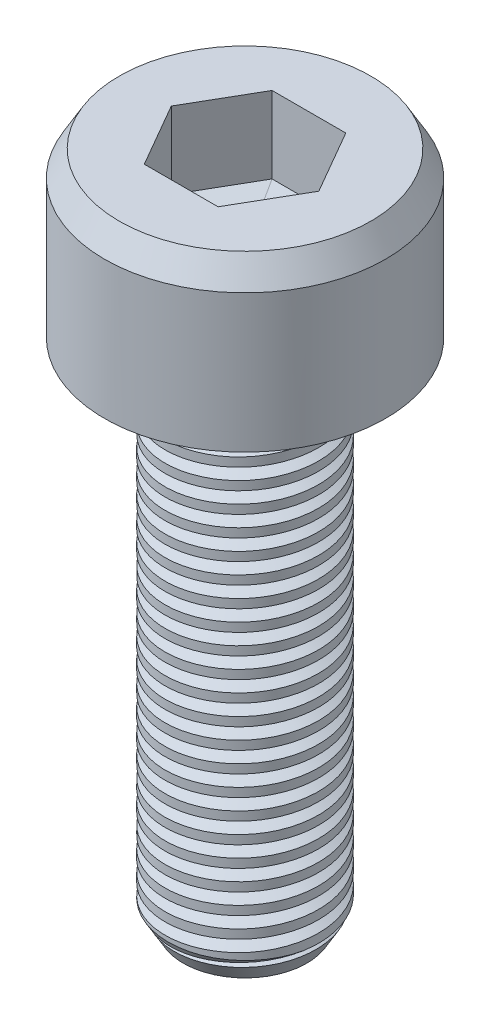
SolidWorks part; units mm, degrees
ref_plane "Front Plane" through (0, 0, 0) normal (0, 0, 1) x (1, 0, 0)
ref_plane "Top Plane" through (0, 0, 0) normal (0, 1, 0) x (1, 0, 0)
ref_plane "Right Plane" through (0, 0, 0) normal (1, 0, 0) x (0, 0, -1)
sketch "Sketch1" plane through (0, 0, 0) normal (0, 1, 0) x (1, 0, 0)
  circle A0 centre (0, 0) radius 2.75
  dimension "D1" = 5.5
extrude "Boss-Extrude1" add sketch "Sketch1" along normal blind 2.7
sketch "Sketch2" plane through (0, 2.7, 0) normal (0, 1, 0) x (1, 0, 0)
  circle A0 centre (0, 0) radius 2.75
  circle A1 centre (0, 0) radius 2.75 construction
  dimension "D1" = 5.5
extrude "Boss-Extrude2" add sketch "Sketch2" along normal blind 0.5 draft 30
sketch "Sketch5" plane through (0, 3.2, 0) normal (0, 1, 0) x (1, 0, 0)
  line L1 (1.4434, 0) -> (0.7217, 1.25)
  line L2 (0.7217, 1.25) -> (-0.7217, 1.25)
  line L3 (-0.7217, 1.25) -> (-1.4434, 0)
  line L4 (-1.4434, 0) -> (-0.7217, -1.25)
  line L5 (-0.7217, -1.25) -> (0.7217, -1.25)
  line L6 (0.7217, -1.25) -> (1.4434, 0)
  circle A0 centre (0, 0) radius 1.25 construction
  circle A1 centre (0, 0) radius 2.4613 construction
  dimension "D1" = 2.5
extrude "Cut-Extrude3" cut sketch "Sketch5" against normal blind 1.5
sketch "Sketch6" plane through (0, 1.7, 0) normal (0, 1, 0) x (1, 0, 0)
  line L0 (1.4434, 0) -> (0.7217, 1.25) construction
  line L1 (1.4434, 0) -> (0.7217, 1.25)
  line L2 (0.7217, 1.25) -> (-0.7217, 1.25)
  line L3 (-0.7217, 1.25) -> (-1.4434, 0)
  line L4 (-1.4434, 0) -> (-0.7217, -1.25)
  line L5 (-0.7217, -1.25) -> (0.7217, -1.25)
  line L6 (0.7217, -1.25) -> (1.4434, 0)
  circle A0 centre (0, 0) radius 1.25 construction
extrude "Cut-Extrude4" cut sketch "Sketch6" against normal blind 0.25 draft 80
sketch "Sketch7" plane through (0, 0, 0) normal (0, -1, 0) x (1, 0, 0)
  circle A0 centre (0, 0) radius 1.5
  circle A1 centre (0, 0) radius 2.75 construction
  dimension "D1" = 3
extrude "Boss-Extrude3" add sketch "Sketch7" along normal blind 9.5
sketch "Sketch8" plane through (0, -9.5, 0) normal (0, -1, 0) x (1, 0, 0)
  circle A0 centre (0, 0) radius 1.5
  circle A1 centre (0, 0) radius 1.5 construction
  dimension "D1" = 3
extrude "Boss-Extrude4" add sketch "Sketch8" along normal blind 0.5 draft 30
sketch "Sketch9" plane through (0, -10, 0) normal (0, -1, 0) x (1, 0, 0)
  circle A0 centre (0, 0) radius 1.5
  circle A1 centre (0, 0) radius 1.2113 construction
  dimension "D1" = 3
curve "Helix/Spiral1" pitch 0.4 height 10 radius 1.5 centre (0, -10, 0) axis (0, 1, 0) start towards (1, 0, 0)
sketch "Sketch10" plane through (0, 0, 0) normal (0, 0, 1) x (1, 0, 0)
  line L1 (1.3037, -10) -> (1.5981, -10.17)
  line L2 (1.5981, -10.17) -> (1.5981, -9.83)
  line L3 (1.5981, -9.83) -> (1.3037, -10)
  circle A0 centre (1.5, -10) radius 0.0981 construction
  spline S0 degree 3 poles (1.5, -10) (1.5, -9.9917) (1.4219, -9.975) (1.0883, -9.95) (0.589, -9.925) (0, -9.9) (-0.589, -9.875) (-1.0883, -9.85) (-1.4219, -9.825) (-1.5391, -9.8) (-1.4219, -9.775) (-1.0883, -9.75) (-0.589, -9.725) (0, -9.7) (0.589, -9.675) (1.0883, -9.65) (1.4219, -9.625) (1.5391, -9.6) (1.4219, -9.575) (1.0883, -9.55) (0.589, -9.525) (0, -9.5) (-0.589, -9.475) (-1.0883, -9.45) (-1.4219, -9.425) (-1.5391, -9.4) (-1.4219, -9.375) (-1.0883, -9.35) (-0.589, -9.325) (0, -9.3) (0.589, -9.275) (1.0883, -9.25) (1.4219, -9.225) (1.5391, -9.2) (1.4219, -9.175) (1.0883, -9.15) (0.589, -9.125) (0, -9.1) (-0.589, -9.075) (-1.0883, -9.05) (-1.4219, -9.025) (-1.5391, -9) (-1.4219, -8.975) (-1.0883, -8.95) (-0.589, -8.925) (0, -8.9) (0.589, -8.875) (1.0883, -8.85) (1.4219, -8.825) (1.5391, -8.8) (1.4219, -8.775) (1.0883, -8.75) (0.589, -8.725) (0, -8.7) (-0.589, -8.675) (-1.0883, -8.65) (-1.4219, -8.625) (-1.5391, -8.6) (-1.4219, -8.575) (-1.0883, -8.55) (-0.589, -8.525) (0, -8.5) (0.589, -8.475) (1.0883, -8.45) (1.4219, -8.425) (1.5391, -8.4) (1.4219, -8.375) (1.0883, -8.35) (0.589, -8.325) (0, -8.3) (-0.589, -8.275) (-1.0883, -8.25) (-1.4219, -8.225) (-1.5391, -8.2) (-1.4219, -8.175) (-1.0883, -8.15) (-0.589, -8.125) (0, -8.1) (0.589, -8.075) (1.0883, -8.05) (1.4219, -8.025) (1.5391, -8) (1.4219, -7.975) (1.0883, -7.95) (0.589, -7.925) (0, -7.9) (-0.589, -7.875) (-1.0883, -7.85) (-1.4219, -7.825) (-1.5391, -7.8) (-1.4219, -7.775) (-1.0883, -7.75) (-0.589, -7.725) (0, -7.7) (0.589, -7.675) (1.0883, -7.65) (1.4219, -7.625) (1.5391, -7.6) (1.4219, -7.575) (1.0883, -7.55) (0.589, -7.525) (0, -7.5) (-0.589, -7.475) (-1.0883, -7.45) (-1.4219, -7.425) (-1.5391, -7.4) (-1.4219, -7.375) (-1.0883, -7.35) (-0.589, -7.325) (0, -7.3) (0.589, -7.275) (1.0883, -7.25) (1.4219, -7.225) (1.5391, -7.2) (1.4219, -7.175) (1.0883, -7.15) (0.589, -7.125) (0, -7.1) (-0.589, -7.075) (-1.0883, -7.05) (-1.4219, -7.025) (-1.5391, -7) (-1.4219, -6.975) (-1.0883, -6.95) (-0.589, -6.925) (0, -6.9) (0.589, -6.875) (1.0883, -6.85) (1.4219, -6.825) (1.5391, -6.8) (1.4219, -6.775) (1.0883, -6.75) (0.589, -6.725) (0, -6.7) (-0.589, -6.675) (-1.0883, -6.65) (-1.4219, -6.625) (-1.5391, -6.6) (-1.4219, -6.575) (-1.0883, -6.55) (-0.589, -6.525) (0, -6.5) (0.589, -6.475) (1.0883, -6.45) (1.4219, -6.425) (1.5391, -6.4) (1.4219, -6.375) (1.0883, -6.35) (0.589, -6.325) (0, -6.3) (-0.589, -6.275) (-1.0883, -6.25) (-1.4219, -6.225) (-1.5391, -6.2) (-1.4219, -6.175) (-1.0883, -6.15) (-0.589, -6.125) (0, -6.1) (0.589, -6.075) (1.0883, -6.05) (1.4219, -6.025) (1.5391, -6) (1.4219, -5.975) (1.0883, -5.95) (0.589, -5.925) (0, -5.9) (-0.589, -5.875) (-1.0883, -5.85) (-1.4219, -5.825) (-1.5391, -5.8) (-1.4219, -5.775) (-1.0883, -5.75) (-0.589, -5.725) (0, -5.7) (0.589, -5.675) (1.0883, -5.65) (1.4219, -5.625) (1.5391, -5.6) (1.4219, -5.575) (1.0883, -5.55) (0.589, -5.525) (0, -5.5) (-0.589, -5.475) (-1.0883, -5.45) (-1.4219, -5.425) (-1.5391, -5.4) (-1.4219, -5.375) (-1.0883, -5.35) (-0.589, -5.325) (0, -5.3) (0.589, -5.275) (1.0883, -5.25) (1.4219, -5.225) (1.5391, -5.2) (1.4219, -5.175) (1.0883, -5.15) (0.589, -5.125) (0, -5.1) (-0.589, -5.075) (-1.0883, -5.05) (-1.4219, -5.025) (-1.5391, -5) (-1.4219, -4.975) (-1.0883, -4.95) (-0.589, -4.925) (0, -4.9) (0.589, -4.875) (1.0883, -4.85) (1.4219, -4.825) (1.5391, -4.8) (1.4219, -4.775) (1.0883, -4.75) (0.589, -4.725) (0, -4.7) (-0.589, -4.675) (-1.0883, -4.65) (-1.4219, -4.625) (-1.5391, -4.6) (-1.4219, -4.575) (-1.0883, -4.55) (-0.589, -4.525) (0, -4.5) (0.589, -4.475) (1.0883, -4.45) (1.4219, -4.425) (1.5391, -4.4) (1.4219, -4.375) (1.0883, -4.35) (0.589, -4.325) (0, -4.3) (-0.589, -4.275) (-1.0883, -4.25) (-1.4219, -4.225) (-1.5391, -4.2) (-1.4219, -4.175) (-1.0883, -4.15) (-0.589, -4.125) (0, -4.1) (0.589, -4.075) (1.0883, -4.05) (1.4219, -4.025) (1.5391, -4) (1.4219, -3.975) (1.0883, -3.95) (0.589, -3.925) (0, -3.9) (-0.589, -3.875) (-1.0883, -3.85) (-1.4219, -3.825) (-1.5391, -3.8) (-1.4219, -3.775) (-1.0883, -3.75) (-0.589, -3.725) (0, -3.7) (0.589, -3.675) (1.0883, -3.65) (1.4219, -3.625) (1.5391, -3.6) (1.4219, -3.575) (1.0883, -3.55) (0.589, -3.525) (0, -3.5) (-0.589, -3.475) (-1.0883, -3.45) (-1.4219, -3.425) (-1.5391, -3.4) (-1.4219, -3.375) (-1.0883, -3.35) (-0.589, -3.325) (0, -3.3) (0.589, -3.275) (1.0883, -3.25) (1.4219, -3.225) (1.5391, -3.2) (1.4219, -3.175) (1.0883, -3.15) (0.589, -3.125) (0, -3.1) (-0.589, -3.075) (-1.0883, -3.05) (-1.4219, -3.025) (-1.5391, -3) (-1.4219, -2.975) (-1.0883, -2.95) (-0.589, -2.925) (0, -2.9) (0.589, -2.875) (1.0883, -2.85) (1.4219, -2.825) (1.5391, -2.8) (1.4219, -2.775) (1.0883, -2.75) (0.589, -2.725) (0, -2.7) (-0.589, -2.675) (-1.0883, -2.65) (-1.4219, -2.625) (-1.5391, -2.6) (-1.4219, -2.575) (-1.0883, -2.55) (-0.589, -2.525) (0, -2.5) (0.589, -2.475) (1.0883, -2.45) (1.4219, -2.425) (1.5391, -2.4) (1.4219, -2.375) (1.0883, -2.35) (0.589, -2.325) (0, -2.3) (-0.589, -2.275) (-1.0883, -2.25) (-1.4219, -2.225) (-1.5391, -2.2) (-1.4219, -2.175) (-1.0883, -2.15) (-0.589, -2.125) (0, -2.1) (0.589, -2.075) (1.0883, -2.05) (1.4219, -2.025) (1.5391, -2) (1.4219, -1.975) (1.0883, -1.95) (0.589, -1.925) (0, -1.9) (-0.589, -1.875) (-1.0883, -1.85) (-1.4219, -1.825) (-1.5391, -1.8) (-1.4219, -1.775) (-1.0883, -1.75) (-0.589, -1.725) (0, -1.7) (0.589, -1.675) (1.0883, -1.65) (1.4219, -1.625) (1.5391, -1.6) (1.4219, -1.575) (1.0883, -1.55) (0.589, -1.525) (0, -1.5) (-0.589, -1.475) (-1.0883, -1.45) (-1.4219, -1.425) (-1.5391, -1.4) (-1.4219, -1.375) (-1.0883, -1.35) (-0.589, -1.325) (0, -1.3) (0.589, -1.275) (1.0883, -1.25) (1.4219, -1.225) (1.5391, -1.2) (1.4219, -1.175) (1.0883, -1.15) (0.589, -1.125) (0, -1.1) (-0.589, -1.075) (-1.0883, -1.05) (-1.4219, -1.025) (-1.5391, -1) (-1.4219, -0.975) (-1.0883, -0.95) (-0.589, -0.925) (0, -0.9) (0.589, -0.875) (1.0883, -0.85) (1.4219, -0.825) (1.5391, -0.8) (1.4219, -0.775) (1.0883, -0.75) (0.589, -0.725) (0, -0.7) (-0.589, -0.675) (-1.0883, -0.65) (-1.4219, -0.625) (-1.5391, -0.6) (-1.4219, -0.575) (-1.0883, -0.55) (-0.589, -0.525) (0, -0.5) (0.589, -0.475) (1.0883, -0.45) (1.4219, -0.425) (1.5391, -0.4) (1.4219, -0.375) (1.0883, -0.35) (0.589, -0.325) (0, -0.3) (-0.589, -0.275) (-1.0883, -0.25) (-1.4219, -0.225) (-1.5391, -0.2) (-1.4219, -0.175) (-1.0883, -0.15) (-0.589, -0.125) (0, -0.1) (0.589, -0.075) (1.0883, -0.05) (1.4219, -0.025) (1.5, -0.0083) (1.5, 0) knots 0 0 0 0 0.0025 0.005 0.0075 0.01 0.0125 0.015 0.0175 0.02 0.0225 0.025 0.0275 0.03 0.0325 0.035 0.0375 0.04 0.0425 0.045 0.0475 0.05 0.0525 0.055 0.0575 0.06 0.0625 0.065 0.0675 0.07 0.0725 0.075 0.0775 0.08 0.0825 0.085 0.0875 0.09 0.0925 0.095 0.0975 0.1 0.1025 0.105 0.1075 0.11 0.1125 0.115 0.1175 0.12 0.1225 0.125 0.1275 0.13 0.1325 0.135 0.1375 0.14 0.1425 0.145 0.1475 0.15 0.1525 0.155 0.1575 0.16 0.1625 0.165 0.1675 0.17 0.1725 0.175 0.1775 0.18 0.1825 0.185 0.1875 0.19 0.1925 0.195 0.1975 0.2 0.2025 0.205 0.2075 0.21 0.2125 0.215 0.2175 0.22 0.2225 0.225 0.2275 0.23 0.2325 0.235 0.2375 0.24 0.2425 0.245 0.2475 0.25 0.2525 0.255 0.2575 0.26 0.2625 0.265 0.2675 0.27 0.2725 0.275 0.2775 0.28 0.2825 0.285 0.2875 0.29 0.2925 0.295 0.2975 0.3 0.3025 0.305 0.3075 0.31 0.3125 0.315 0.3175 0.32 0.3225 0.325 0.3275 0.33 0.3325 0.335 0.3375 0.34 0.3425 0.345 0.3475 0.35 0.3525 0.355 0.3575 0.36 0.3625 0.365 0.3675 0.37 0.3725 0.375 0.3775 0.38 0.3825 0.385 0.3875 0.39 0.3925 0.395 0.3975 0.4 0.4025 0.405 0.4075 0.41 0.4125 0.415 0.4175 0.42 0.4225 0.425 0.4275 0.43 0.4325 0.435 0.4375 0.44 0.4425 0.445 0.4475 0.45 0.4525 0.455 0.4575 0.46 0.4625 0.465 0.4675 0.47 0.4725 0.475 0.4775 0.48 0.4825 0.485 0.4875 0.49 0.4925 0.495 0.4975 0.5 0.5025 0.505 0.5075 0.51 0.5125 0.515 0.5175 0.52 0.5225 0.525 0.5275 0.53 0.5325 0.535 0.5375 0.54 0.5425 0.545 0.5475 0.55 0.5525 0.555 0.5575 0.56 0.5625 0.565 0.5675 0.57 0.5725 0.575 0.5775 0.58 0.5825 0.585 0.5875 0.59 0.5925 0.595 0.5975 0.6 0.6025 0.605 0.6075 0.61 0.6125 0.615 0.6175 0.62 0.6225 0.625 0.6275 0.63 0.6325 0.635 0.6375 0.64 0.6425 0.645 0.6475 0.65 0.6525 0.655 0.6575 0.66 0.6625 0.665 0.6675 0.67 0.6725 0.675 0.6775 0.68 0.6825 0.685 0.6875 0.69 0.6925 0.695 0.6975 0.7 0.7025 0.705 0.7075 0.71 0.7125 0.715 0.7175 0.72 0.7225 0.725 0.7275 0.73 0.7325 0.735 0.7375 0.74 0.7425 0.745 0.7475 0.75 0.7525 0.755 0.7575 0.76 0.7625 0.765 0.7675 0.77 0.7725 0.775 0.7775 0.78 0.7825 0.785 0.7875 0.79 0.7925 0.795 0.7975 0.8 0.8025 0.805 0.8075 0.81 0.8125 0.815 0.8175 0.82 0.8225 0.825 0.8275 0.83 0.8325 0.835 0.8375 0.84 0.8425 0.845 0.8475 0.85 0.8525 0.855 0.8575 0.86 0.8625 0.865 0.8675 0.87 0.8725 0.875 0.8775 0.88 0.8825 0.885 0.8875 0.89 0.8925 0.895 0.8975 0.9 0.9025 0.905 0.9075 0.91 0.9125 0.915 0.9175 0.92 0.9225 0.925 0.9275 0.93 0.9325 0.935 0.9375 0.94 0.9425 0.945 0.9475 0.95 0.9525 0.955 0.9575 0.96 0.9625 0.965 0.9675 0.97 0.9725 0.975 0.9775 0.98 0.9825 0.985 0.9875 0.99 0.9925 0.995 0.9975 1 1 1 1 construction
  dimension "D1" = 0.1963
  dimension "D2" = 1.3037
sweep "Cut-Sweep1" cut profiles "Sketch10" path "Helix/Spiral1" align with end faces yes
